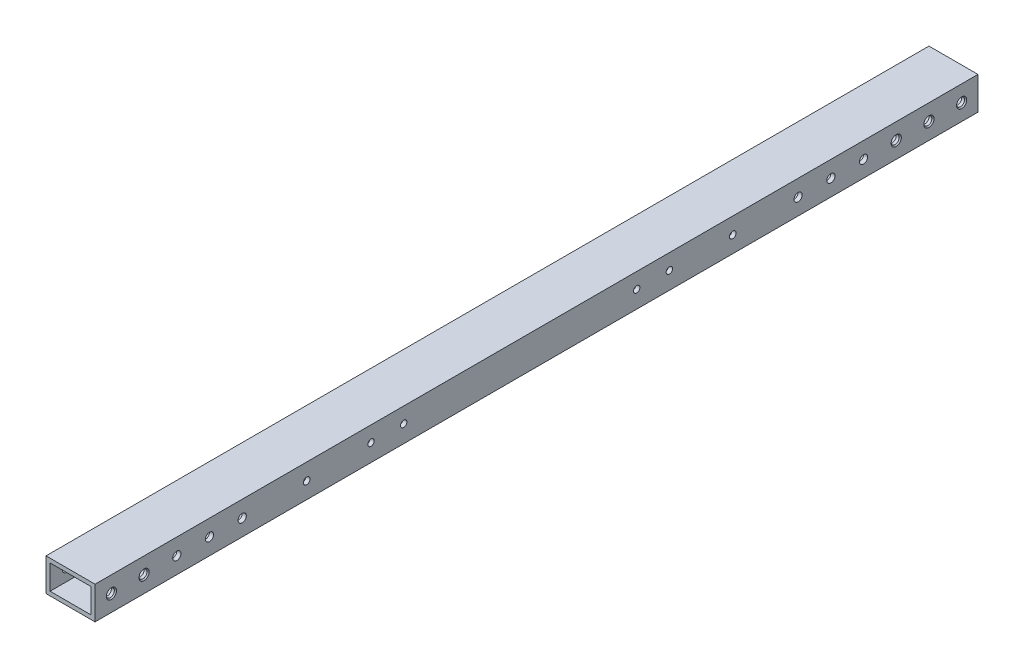
SolidWorks part; units mm, degrees
ref_plane "Front Plane" through (0, 0, 0) normal (0, 0, 1) x (1, 0, 0)
ref_plane "Top Plane" through (0, 0, 0) normal (0, 1, 0) x (1, 0, 0)
ref_plane "Right Plane" through (0, 0, 0) normal (1, 0, 0) x (0, 0, -1)
sketch "Sketch1" plane through (0, 0, 0) normal (0, 0, 1) x (1, 0, 0)
  line L0 (-15.875, 9.525) -> (15.875, 9.525)
  line L2 (-19.05, 12.7) -> (19.05, 12.7)
  line L3 (-19.05, 12.7) -> (-19.05, -12.7)
  line L4 (-19.05, -12.7) -> (19.05, -12.7)
  line L5 (19.05, 12.7) -> (19.05, -12.7)
  line L10 (15.875, 9.525) -> (15.875, -9.525)
  line L11 (-15.875, -9.525) -> (15.875, -9.525)
  line L12 (-15.875, 9.525) -> (-15.875, -9.525)
  point P12 (0, 12.7)
  point P14 (19.05, 0)
  dimension "Wall Thickness" = 3.175
  dimension "Outside Width" = 38.1
  dimension "Outside Height" = 25.4
  dimension "Inside Height" = 19.05
  dimension "Inside Width" = 31.75
sketch "Sketch2" plane through (0, 0, 0) normal (1, 0, 0) x (0, 0, -1)
  line L0 (342.9, 0) -> (-342.9, 0)
  point P4 (0, 0)
  point P7 (-342.9, 0)
  point P10 (342.9, 0)
  dimension "Length" = 685.8
sketch "Sketch3" plane through (0, 0, 0) normal (0, 0, 1) x (1, 0, 0)
  line L21 (19.05, 12.7) -> (-19.05, 12.7)
  line L22 (19.05, -12.7) -> (19.05, 12.7)
  line L23 (-19.05, -12.7) -> (19.05, -12.7)
  line L24 (-19.05, 12.7) -> (-19.05, -12.7)
  line L25 (19.05, 12.7) -> (-19.05, 12.7)
  line L26 (19.05, -12.7) -> (19.05, 12.7)
  line L27 (-19.05, -12.7) -> (19.05, -12.7)
  line L28 (-19.05, 12.7) -> (-19.05, -12.7)
  line L29 (15.875, 9.525) -> (-15.875, 9.525)
  line L30 (15.875, -9.525) -> (15.875, 9.525)
  line L31 (-15.875, -9.525) -> (15.875, -9.525)
  line L32 (-15.875, 9.525) -> (-15.875, -9.525)
  line L33 (15.875, 9.525) -> (-15.875, 9.525)
  line L34 (15.875, -9.525) -> (15.875, 9.525)
  line L35 (-15.875, -9.525) -> (15.875, -9.525)
  line L36 (-15.875, 9.525) -> (-15.875, -9.525)
  dimension "D1" = 0
  dimension "D2" = 0
extrude "Boss-Extrude1" add sketch "Sketch3" along normal up to vertex (342.9 mm away) and the other way up to vertex (342.9 mm away) up to point (0, 0, 342.9) other way up to point (0, 0, -342.9)
sketch "Drawing Reference" plane through (0, 0, 0) normal (1, 0, 0) x (0, 0, -1)
  line L0 (-342.9, 0) -> (342.9, 0) construction
  line L1 (0, -12.7) -> (0, 12.7) construction
  line L2 (-342.9, -12.7) -> (342.9, -12.7) construction
  line L5 (-342.9, 12.7) -> (342.9, 12.7) construction
  point P7 (-315.468, 0)
  point P8 (315.468, 0)
  dimension "D1" = 27.432
sketch "Sketch4" plane through (-19.05, 0, 0) normal (-1, 0, 0) x (0, 0, 1)
  line L0 (-342.9, 0) -> (-330.2, 0)
  line L1 (-342.9, 12.7) -> (-342.9, -12.7) construction
  line L2 (-330.2, 0) -> (-304.8, 0)
  line L3 (-304.8, 0) -> (-279.4, 0)
  line L4 (-279.4, 0) -> (-254, 0)
  line L5 (-254, 0) -> (-228.6, 0)
  line L6 (-228.6, 0) -> (-203.2, 0)
  line L7 (342.9, 0) -> (330.2, 0)
  line L8 (342.9, 12.7) -> (342.9, -12.7) construction
  line L9 (330.2, 0) -> (304.8, 0)
  line L10 (304.8, 0) -> (279.4, 0)
  line L11 (279.4, 0) -> (254, 0)
  line L12 (254, 0) -> (228.6, 0)
hole_wizard "1/4 (0.25) Diameter Hole2" positions "Sketch7" profile "Sketch8" hole size "1/4" standard "ANSI Inch" end condition through all
sketch "Sketch7" plane through (-19.05, 0, 0) normal (-1, 0, 0) x (0, 0, 1)
  point P0 (-330.2, 0)
  point P3 (-304.8, 0)
  point P7 (330.2, 0)
  point P11 (-279.4, 0)
  point P14 (304.8, 0)
sketch "Sketch8" plane through (-19.05, 0, -330.2) normal (0, 1, 0) x (0, 0, 1)
  line L0 (0, 0) -> (0, 38.1)
  line L1 (0, 38.1) -> (3.9624, 38.1)
  line L2 (3.175, 37.1942) -> (3.175, 0)
  line L5 (3.175, 0) -> (0, 0)
  line L7 (3.9624, 38.1) -> (3.175, 37.1942)
  line L8 (-3.9624, 38.1) -> (-3.175, 37.1942) construction
  line L11 (0, -6.35) -> (0, 107.95) construction
  dimension "Thru Hole Dia." = 6.35
  dimension "Thru Hole Depth" = 38.1
  dimension "Far C'Sink Dia." = 7.9248
  dimension "Far C'Sink Angle" = 82
hole_wizard "1/4 (0.25) Diameter Hole3" positions "Sketch9" profile "Sketch10" hole size "1/4" standard "ANSI Inch" end condition through all
sketch "Sketch9" plane through (19.05, 0, 0) normal (1, 0, 0) x (0, 0, -1)
  point P0 (-279.4, 0)
  point P3 (-254, 0)
  point P6 (-228.6, 0)
  point P9 (254, 0)
  point P12 (228.6, 0)
  point P15 (203.2, 0)
sketch "Sketch10" plane through (19.05, 0, 279.4) normal (0, 1, 0) x (0, 0, -1)
  line L0 (0, 0) -> (0, 38.1)
  line L1 (0, 38.1) -> (3.175, 38.1)
  line L2 (3.175, 38.1) -> (3.175, 0)
  line L5 (3.175, 0) -> (0, 0)
  line L11 (0, -6.35) -> (0, 107.95) construction
  dimension "Thru Hole Dia." = 6.35
  dimension "Thru Hole Depth" = 38.1
hole_wizard "13/64 (0.20313) Diameter Hole1" positions "Sketch11" profile "Sketch12" hole size "13/64" standard "ANSI Inch" end condition through all
sketch "Sketch11" plane through (19.05, 0, 0) normal (1, 0, 0) x (0, 0, -1)
  point P0 (152.4, 0)
  point P3 (-178.5118, 0)
sketch "Sketch12" plane through (19.05, 0, -152.4) normal (0, 1, 0) x (0, 0, -1)
  line L0 (0, 0) -> (0, 38.1)
  line L1 (0, 38.1) -> (2.5798, 38.1)
  line L2 (2.5798, 38.1) -> (2.5798, 0)
  line L5 (2.5798, 0) -> (0, 0)
  line L11 (0, -6.35) -> (0, 107.95) construction
  dimension "Thru Hole Dia." = 5.1595
  dimension "Thru Hole Depth" = 38.1
sketch "Sketch13" plane through (19.05, 0, 0) normal (1, 0, 0) x (0, 0, -1)
  line L0 (-103.5434, 0.3445) -> (-128.9434, 0.3445)
  line L1 (77.7875, 0.7112) -> (102.8316, 0.7112)
hole_wizard "#10 Clearance Hole1" positions "Sketch14" profile "Sketch15" hole size "#10" standard "ANSI Inch" end condition through all
sketch "Sketch14" plane through (19.05, 0, 0) normal (1, 0, 0) x (0, 0, -1)
  point P19 (-128.5875, 0.7112)
  point P22 (-103.1875, 0.7112)
  point P35 (77.7875, 0.7112)
  point P38 (103.1875, 0.7112)
sketch "Sketch15" plane through (19.05, 0.7112, 128.5875) normal (0, 1, 0) x (0, 0, -1)
  line L0 (0, 0) -> (0, 38.1)
  line L1 (0, 38.1) -> (2.4892, 38.1)
  line L2 (2.4892, 38.1) -> (2.4892, 0)
  line L5 (2.4892, 0) -> (0, 0)
  line L11 (0, -6.35) -> (0, 107.95) construction
  dimension "Thru Hole Dia." = 4.9784
  dimension "Thru Hole Depth" = 38.1
equation "\"D1@Drawing Reference\"=\"Outside Width@Sketch1\" * 0.72"
